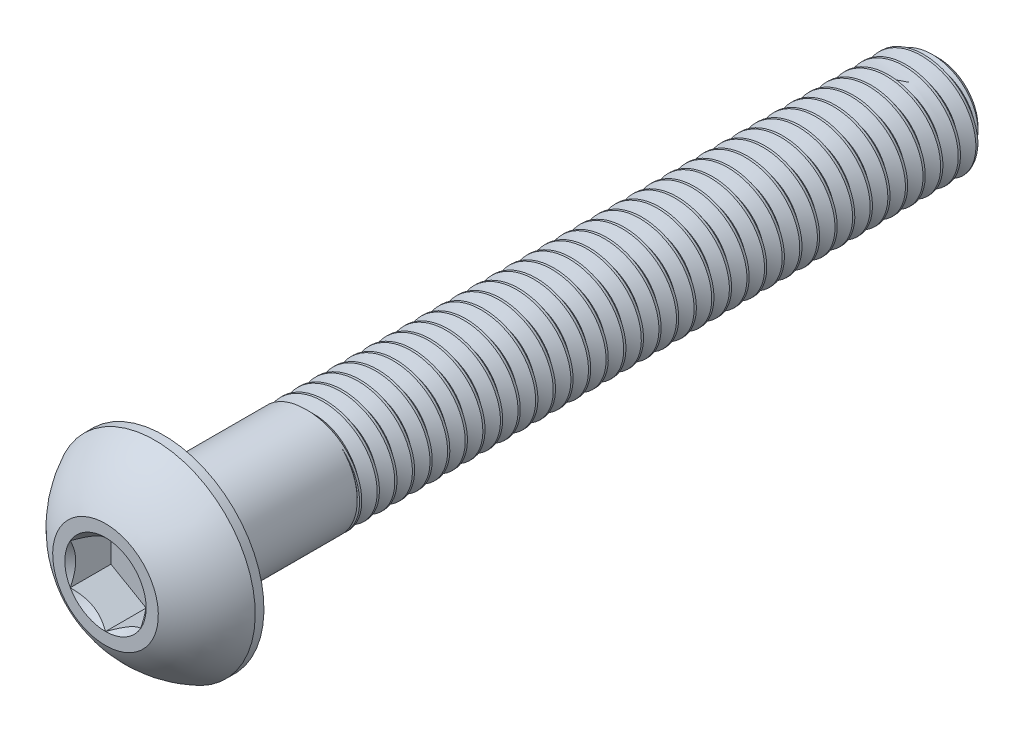
SolidWorks part; units mm, degrees
ref_plane "Front" through (0, 0, 0) normal (0, 0, 1) x (1, 0, 0)
ref_plane "Top" through (0, 0, 0) normal (0, 1, 0) x (1, 0, 0)
ref_plane "Right" through (0, 0, 0) normal (1, 0, 0) x (0, 0, -1)
sketch "Sketch1" plane through (0, 0, 0) normal (1, 0, 0) x (0, 0, -1)
  line L2 (-11, 1.5) -> (11, 1.5)
  line L3 (11, 1.5) -> (11, 0)
  line L4 (11, 0) -> (-11, 0)
  line L6 (-11.2475, 2.85) -> (-11, 2.85) construction
  line L7 (11, 1.5) -> (11, -1.5) construction
  line L8 (-12.65, 0) -> (-11, 0) construction
  line L9 (-11, 2.85) -> (-11, -2.85) construction
  line L11 (-11, 1.5) -> (-11, 0)
  line L13 (-12.65, 1) -> (-12.65, -1) construction
  line L14 (-12.65, 1) -> (-12.65, 1.5) construction
  line L15 (10.9688, 1.5541) -> (11.2188, 1.1211) construction
  line L16 (11.2188, 1.1211) -> (11.4688, 1.5541) construction
  line L17 (11.4688, 1.5541) -> (10.9688, 1.5541) construction
  line L18 (11, 1.5) -> (11.4375, 1.5) construction
  line L19 (11.2188, 1.5541) -> (11.2188, 1.5) construction
  line L20 (11.2188, 1.5) -> (11.2188, 1.1752) construction
  line L21 (11.2188, 1.1752) -> (11.2188, 1.1211) construction
  line L22 (11.1875, 1.1752) -> (11.25, 1.1752)
  line L23 (10.9844, 1.5271) -> (11.4531, 1.5271)
  line L24 (11.25, 1.1752) -> (11.4531, 1.5271)
  line L25 (11.1875, 1.1752) -> (10.9844, 1.5271)
  line L26 (10.625, 1.5) -> (11, 1.125)
  arc A3 (-12.65, 1.5) -> (-11.2475, 2.85) centre (-9.8552, 0) cw construction
  point P29 (11.2188, 1.5271)
  point P30 (9.75, -1.5)
  point P32 (-7, 1.5)
  point P33 (-12, 0)
  point P34 (0, 0)
  point P35 (-6, 0)
  dimension "Thread Size" = 3
  dimension "D1" = 0.2475
  dimension "Head Height" = 1.65
  dimension "Head Diameter" = 5.7
  dimension "Length" = 22
  dimension "Drive Size" = 2
  dimension "Thread Pitch" = 0.5
  dimension "D3" = 0.0625
  dimension "D2" = 0.375
  dimension "D4" = 45
  dimension "D5" = 1.25
  dimension "Minimum Thread Length" = 18
  dimension "D6" = 5
  dimension "D7" = 5
sketch "Sketch10" plane through (0, 0, 0) normal (1, 0, 0) x (0, 0, -1)
  line L0 (10.625, 1.5) -> (11, 1.125) construction
  line L1 (10.625, 1.5) -> (11, 1.125)
  line L4 (11, 1.5) -> (-11, 1.5)
  line L5 (11, 0) -> (11, 1.5)
  line L6 (-11, 0) -> (11, 0)
  line L7 (-11, 1.5) -> (-11, 0)
  line L8 (10.625, 1.5) -> (-11, 1.5)
  line L9 (11, 0) -> (11, 1.125)
  line L10 (-11, 0) -> (11, 0)
  line L11 (-11, 1.5) -> (-11, 0)
  dimension "D1" = 0
revolve "Revolve3" add sketch "Sketch10" angle 360 about L8
sketch "Sketch7" plane through (0, 0, 0) normal (1, 0, 0) x (0, 0, -1)
  line L6 (-11.2475, 2.85) -> (-11, 2.85) construction
  line L8 (-12.65, 0) -> (-11, 0) construction
  line L11 (-11, 2.85) -> (-11, -2.85) construction
  line L12 (-11.2475, 2.85) -> (-11, 2.85)
  line L13 (-12.65, 0) -> (-11, 0)
  line L14 (-12.65, 1) -> (-12.65, -1) construction
  line L15 (-11, 2.85) -> (-11, 0)
  line L16 (-12.65, 1.5) -> (-12.65, 0)
  arc A2 (-11.2475, 2.85) -> (-12.65, 1.5) centre (-9.8552, 0) ccw construction
  arc A3 (-11.2475, 2.85) -> (-12.65, 1.5) centre (-9.8552, 0) ccw
revolve "Revolve2" add sketch "Sketch7" angle 360 mid plane about L13
sketch "Sketch5" plane through (0, 0, 12.65) normal (0, 0, 1) x (1, 0, 0)
  line L1 (1, -0.5774) -> (1, 0.5774)
  line L2 (1, 0.5774) -> (0, 1.1547)
  line L3 (0, 1.1547) -> (-1, 0.5774)
  line L4 (-1, 0.5774) -> (-1, -0.5774)
  line L5 (-1, -0.5774) -> (0, -1.1547)
  line L6 (0, -1.1547) -> (1, -0.5774)
  circle A0 centre (0, 0) radius 1 construction
extrude "Cut-Extrude2" cut sketch "Sketch5" against normal blind 1.155
sketch "Sketch6" plane through (0, 0, 12.65) normal (0, 0, 1) x (1, 0, 0)
  circle A0 centre (0, 0) radius 1.1547
extrude "Cut-Extrude3" cut sketch "Sketch6" against normal blind 1.155 draft 45
ref_plane "Plane1" through (0, 0, 7) normal (0, 0, 1) x (1, 0, 0)
sketch "Sketch9" plane through (0, 0, 7) normal (0, 0, -1) x (-1, 0, 0)
  circle A0 centre (0, 0) radius 1.5 construction
  circle A4 centre (0, 0) radius 1.5
split "Split1" trim tools "Plane1" bodies to split 113 resulting bodies 123 124
sketch "Sketch11" plane through (0, 0, -11) normal (0, 0, -1) x (-1, 0, 0)
  circle A0 centre (0, 0) radius 1.5 construction
  circle A1 centre (0, 0) radius 1.5
curve "Helix/Spiral1" pitch 0.5 height 19.65 turns 39.3
sketch "Sketch12" plane through (0, 0, 0) normal (1, 0, 0) x (0, 0, -1)
  line L0 (11.1875, 1.1752) -> (11.25, 1.1752) construction
  line L1 (11.25, 1.1752) -> (11.4531, 1.5271) construction
  line L2 (10.9844, 1.5271) -> (11.4531, 1.5271) construction
  line L3 (11.1875, 1.1752) -> (10.9844, 1.5271) construction
  line L4 (11.1875, 1.1752) -> (11.25, 1.1752)
  line L5 (11.25, 1.1752) -> (11.4531, 1.5271)
  line L6 (10.9844, 1.5271) -> (11.4531, 1.5271)
  line L7 (11.1875, 1.1752) -> (10.9844, 1.5271)
sweep "Cut-Sweep2" cut profiles "Sketch12" path "Helix/Spiral1"
extrude "Boss-Extrude1" add sketch "Sketch9" along normal blind 10 draft 45
equation "\"D1@Cut-Extrude2\" = \"Head Height@Sketch1\" * .7"
equation "\"D1@Sketch1\" = \"Head Height@Sketch1\" * .15"
equation "\"D1@Cut-Extrude3\" = \"D1@Cut-Extrude2\""
equation "\"D3@Sketch1\" = \"Thread Pitch@Sketch1\" / 8"
equation "\"D2@Sketch1\" = \"Thread Pitch@Sketch1\" * 0.75"
equation "\"D3@Helix/Spiral1\"=\"Minimum Thread Length@Sketch1\" + \"Head Height@Sketch1\""
equation "\"D4@Helix/Spiral1\" = \"Thread Pitch@Sketch1\""
equation "\"D5@Sketch1\" = \"Thread Pitch@Sketch1\" * 2.5"
